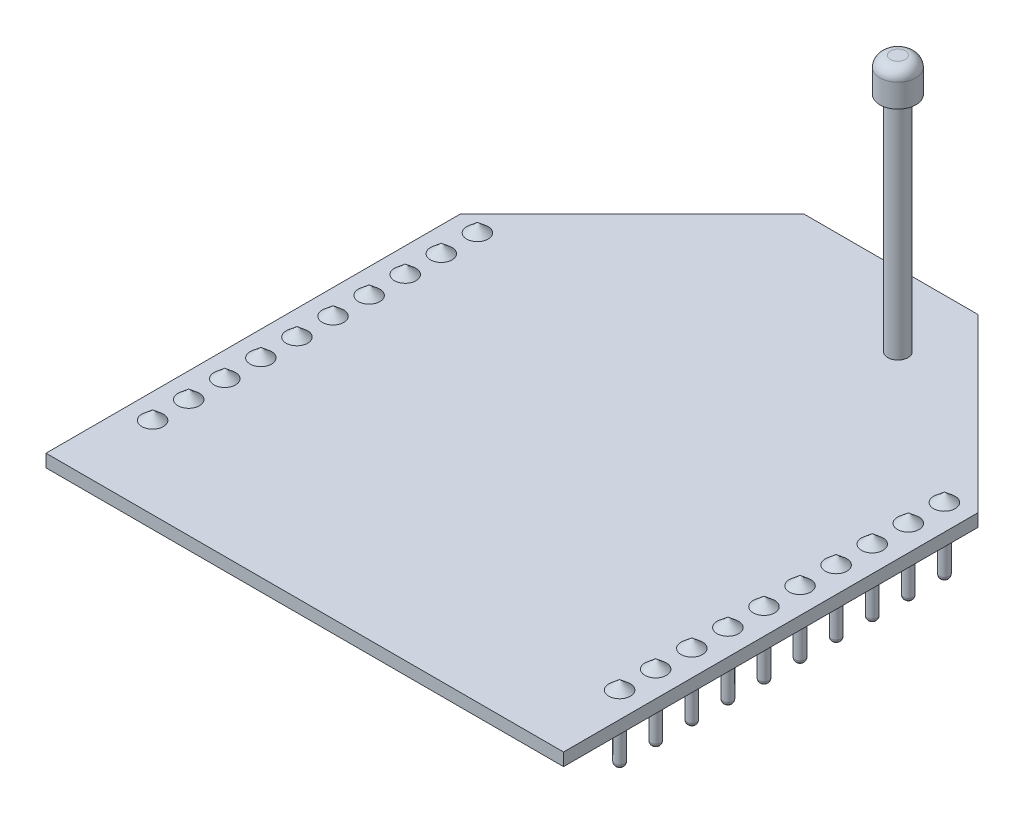
SolidWorks part; units mm, degrees
ref_plane "Front Plane" through (0, 0, 0) normal (0, 0, 1) x (1, 0, 0)
ref_plane "Top Plane" through (0, 0, 0) normal (0, 1, 0) x (1, 0, 0)
ref_plane "Right Plane" through (0, 0, 0) normal (1, 0, 0) x (0, 0, -1)
other "Center of Mass"
sketch "Sketch1" plane through (0, 0, 0) normal (0, 1, 0) x (1, 0, 0)
  line L0 (-7.2145, 10.7595) -> (-15.2997, 2.6743)
  line L1 (-7.2145, 10.7595) -> (0.9951, 10.7595)
  line L2 (-15.2997, 2.6743) -> (-15.2997, -16.8505)
  line L3 (-15.2997, -16.8505) -> (9.0803, -16.8505)
  line L4 (9.0803, 2.6743) -> (9.0803, -16.8505)
  line L5 (-3.1097, 10.7595) -> (-3.1097, -16.8505) construction
  line L6 (0.9951, 10.7595) -> (9.0803, 2.6743)
  circle A0 centre (7.8716, 2.3005) radius 0.5078
  circle A1 centre (-14.1284, 2.3005) radius 0.5078
  circle A2 centre (-14.1284, 0.6005) radius 0.5078
  circle A3 centre (-14.1284, -1.0995) radius 0.5078
  circle A4 centre (-14.1284, -2.7995) radius 0.5078
  circle A5 centre (-14.1284, -4.4995) radius 0.5078
  circle A6 centre (-14.1284, -6.1995) radius 0.5078
  circle A7 centre (-14.1284, -7.8995) radius 0.5078
  circle A8 centre (-14.1284, -9.5995) radius 0.5078
  circle A9 centre (-14.1284, -11.2995) radius 0.5078
  circle A10 centre (-14.1284, -12.9995) radius 0.5078
  circle A11 centre (7.8716, 0.6005) radius 0.5078
  circle A12 centre (7.8716, -1.0995) radius 0.5078
  circle A13 centre (7.8716, -2.7995) radius 0.5078
  circle A14 centre (7.8716, -4.4995) radius 0.5078
  circle A15 centre (7.8716, -6.1995) radius 0.5078
  circle A16 centre (7.8716, -7.8995) radius 0.5078
  circle A17 centre (7.8716, -9.5995) radius 0.5078
  circle A18 centre (7.8716, -11.2995) radius 0.5078
  circle A19 centre (7.8716, -12.9995) radius 0.5078
  dimension "D1" = 2
  dimension "D2" = 10
extrude "Boss-Extrude1" add sketch "Sketch1" against normal blind 0.6 contours L1 L6 L4 L3 L2 L0
extrude "Boss-Extrude2" add sketch "Sketch1<3>" along normal blind 0.5 draft 50 separate body contours A1
sketch "Sketch1<3>" plane through (0, 0, 0) normal (0, 1, 0) x (1, 0, 0) same geometry as "Sketch1"
pattern_linear "LPattern1" count 2 spacing 22 along (1, 0, 0) count 10 spacing 1.7 along (0, 0, 1) of "Boss-Extrude2"
sketch "Sketch2" plane through (0, -0.6, 0) normal (0, -1, 0) x (1, 0, 0)
  circle A0 centre (-14.1284, -2.3005) radius 0.2296
  circle A1 centre (7.8716, -2.3005) radius 0.2296
  circle A2 centre (7.8716, -0.6005) radius 0.2296
  circle A3 centre (7.8716, 1.0995) radius 0.2296
  circle A4 centre (7.8716, 2.7995) radius 0.2296
  circle A5 centre (7.8716, 4.4995) radius 0.2296
  circle A6 centre (7.8716, 6.1995) radius 0.2296
  circle A7 centre (7.8716, 7.8995) radius 0.2296
  circle A8 centre (7.8716, 9.5995) radius 0.2296
  circle A9 centre (7.8716, 11.2995) radius 0.2296
  circle A10 centre (7.8716, 12.9995) radius 0.2296
  circle A11 centre (-14.1284, -0.6005) radius 0.2296
  circle A12 centre (-14.1284, 1.0995) radius 0.2296
  circle A13 centre (-14.1284, 2.7995) radius 0.2296
  circle A14 centre (-14.1284, 4.4995) radius 0.2296
  circle A15 centre (-14.1284, 6.1995) radius 0.2296
  circle A16 centre (-14.1284, 7.8995) radius 0.2296
  circle A17 centre (-14.1284, 9.5995) radius 0.2296
  circle A18 centre (-14.1284, 11.2995) radius 0.2296
  circle A19 centre (-14.1284, 12.9995) radius 0.2296
  dimension "D1" = 2
  dimension "D2" = 10
extrude "Boss-Extrude3" add sketch "Sketch2" along normal blind 2.5
fillet "Fillet1" radius 0.2 1 edges at (-14.1284, -3.1, -2.5301)
fillet "Fillet2" radius 0.2 19 edges at (7.8716, -3.1, 0.8699) (7.8716, -3.1, 2.5699) (7.8716, -3.1, 4.2699) (7.8716, -3.1, 5.9699) (7.8716, -3.1, 9.3699) (7.8716, -3.1, -2.5301) (7.8716, -3.1, -0.8301) (7.8716, -3.1, 7.6699) (7.8716, -3.1, 11.0699) (7.8716, -3.1, 12.7699) (-14.1284, -3.1, 12.7699) (-14.1284, -3.1, 11.0699) (-14.1284, -3.1, 9.3699) (-14.1284, -3.1, 7.6699) (-14.1284, -3.1, 5.9699) (-14.1284, -3.1, 4.2699) (-14.1284, -3.1, 2.5699) (-14.1284, -3.1, 0.8699) (-14.1284, -3.1, -0.8301)
sketch "Sketch3" plane through (0, 0, 0) normal (0, 1, 0) x (1, 0, 0)
  circle A0 centre (0.6293, 7.3513) radius 0.4781
extrude "Boss-Extrude4" add sketch "Sketch3" along normal blind 10.5
sketch "Sketch4" plane through (0, 10.5, 0) normal (0, 1, 0) x (1, 0, 0)
  circle A0 centre (0.6293, 7.3513) radius 0.85
  dimension "D1" = 1.7
extrude "Boss-Extrude5" add sketch "Sketch4" along normal blind 1.6
fillet "Fillet3" radius 0.5 1 edges at (0.6293, 12.1, -6.5013)
